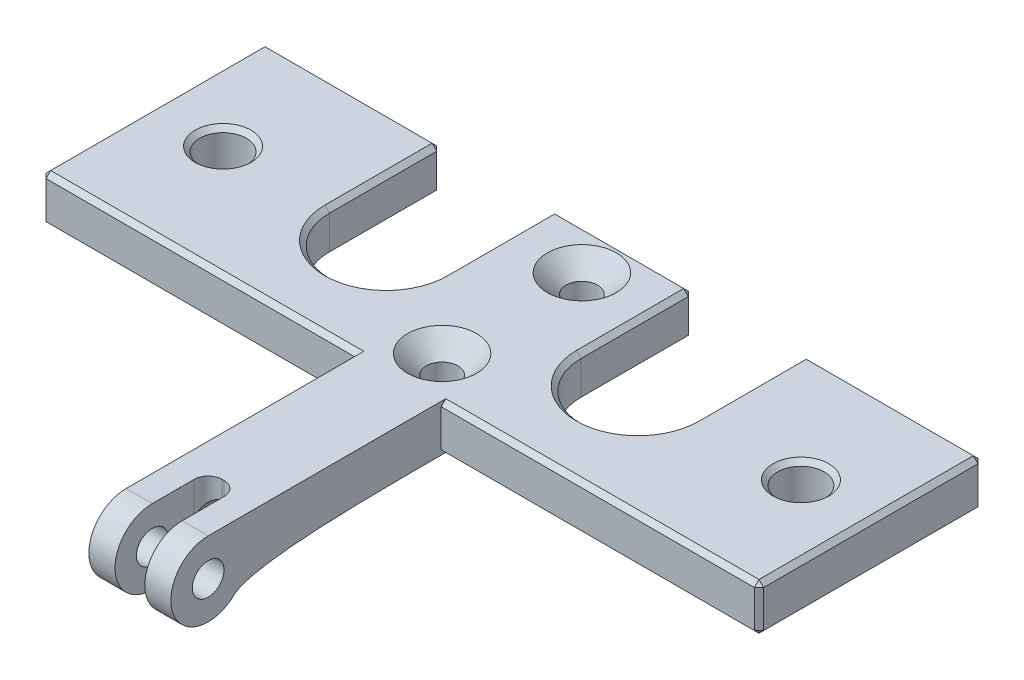
SolidWorks part; units mm, degrees
ref_plane "Front Plane" through (0, 0, 0) normal (0, 0, 1) x (1, 0, 0)
ref_plane "Top Plane" through (0, 0, 0) normal (0, 1, 0) x (1, 0, 0)
ref_plane "Right Plane" through (0, 0, 0) normal (1, 0, 0) x (0, 0, -1)
sketch "Sketch1" plane through (0, 0, 0) normal (0, 1, 0) x (1, 0, 0)
  line L0 (0, 0) -> (0, 50000) construction
  line L1 (38.5, -12) -> (-38.5, -12)
  line L2 (38.5, -12) -> (38.5, 12)
  line L3 (38.5, 12) -> (-38.5, 12)
  line L4 (-38.5, -12) -> (-38.5, 12)
  line L5 (38.5, -12) -> (-38.5, 12) construction
  line L6 (38.5, 12) -> (-38.5, -12) construction
  line L7 (0, 0) -> (50000, 0) construction
  line L8 (-19.575, 0) -> (-19.575, 12)
  line L9 (-7.425, 0) -> (-7.425, 12)
  line L10 (7.425, 0) -> (7.425, 12)
  line L11 (19.575, 0) -> (19.575, 12)
  circle A0 centre (-31, 0) radius 2.5
  circle A1 centre (-13.5, 0) radius 6.075
  circle A2 centre (31, 0) radius 2.5
  circle A3 centre (13.5, 0) radius 6.075
  circle A4 centre (0, -7.5) radius 1.7
  circle A5 centre (0, 7.5) radius 1.7
  point P0 (0, 0)
  dimension "D3" = 27
  dimension "D5" = 5
  dimension "D6" = 12.15
  dimension "D7" = 3.4
  dimension "D1" = 24
  dimension "D2" = 77
  dimension "D4" = 62
  dimension "D8" = 7.5
  dimension "D9" = 7.5
extrude "Boss-Extrude1" add sketch "Sketch1" along normal blind 5 contours L11 A3 L10 L3 L9 A1 L8 L4 L1 L2 A2 A0 region at (0, 0, 1.0489)
chamfer "Chamfer2" distance 2 angle 45 2 edges at (0, 5, -5.8) (0, 5, 9.2)
sketch "Sketch2" plane through (0, 0, 0) normal (0, -1, 0) x (1, 0, 0)
  line L9 (-5.025, 0) -> (-5.025, -12)
  line L10 (-21.975, -12) -> (-21.975, 0)
  line L11 (-5.025, 0) -> (-5.025, -12)
  line L12 (-21.975, -12) -> (-21.975, 0)
  line L14 (21.975, -12) -> (5.025, -12)
  line L15 (-5.025, -12) -> (-21.975, -12)
  line L16 (21.975, 0) -> (21.975, -12)
  line L17 (5.025, -12) -> (5.025, 0)
  line L18 (21.975, 0) -> (21.975, -12)
  line L19 (5.025, -12) -> (5.025, 0)
  arc A7 (-5.025, 0) -> (-21.975, 0) centre (-13.5, 0) ccw
  arc A8 (-5.025, 0) -> (-21.975, 0) centre (-13.5, 0) ccw
  arc A12 (21.975, 0) -> (5.025, 0) centre (13.5, 0) ccw
  arc A13 (21.975, 0) -> (5.025, 0) centre (13.5, 0) ccw
  dimension "D1" = 2.4
  dimension "D2" = 2.4
extrude "Cut-Extrude1" cut sketch "Sketch2" against normal blind 0.4
chamfer "Chamfer3" distance 0.5 angle 45 46 edges at (-31, 0, 2.5) (-31, 5, 2.5) (31, 0, 2.5) (31, 5, 2.5) (19.575, 5, -6) (7.425, 5, -6) (13.5, 5, 6.075) (38.5, 5, 0) (0, 5, 12) (38.5, 2.5, 12) (-38.5, 5, 0) (-38.5, 2.5, 12) (-19.575, 2.7, -12) (-29.0375, 5, -12) (-38.5, 2.5, -12) (-30.2375, 0, -12) (-38.5, 0, 0) (0, 0, 12) (38.5, 0, 0) (38.5, 2.5, -12) (29.0375, 5, -12) (19.575, 2.7, -12) (30.2375, 0, -12) (7.425, 2.7, -12) (0, 5, -12) (-7.425, 2.7, -12) (-19.575, 5, -6) (-7.425, 5, -6) (-13.5, 5, 6.075) (0, 0, 9.2) (0, 0, -5.8) (7.425, 0.4, -6) (19.575, 0.4, -6) (13.5, 0.4, 6.075) (-20.775, 0.4, -12) (-21.975, 0.2, -12) (20.775, 0.4, -12) (21.975, 0.2, -12) (5.025, 0.2, -12) (6.225, 0.4, -12) (-6.225, 0.4, -12) (-5.025, 0.2, -12) (0, 0, -12) (-7.425, 0.4, -6) (-19.575, 0.4, -6) (-13.5, 0.4, 6.075)
sketch "Sketch4" plane through (0, 0, 0) normal (1, 0, 0) x (0, 0, -1)
  line L0 (-12, 0.5) -> (-12, 4.5) construction
  line L1 (-11.5, 5) -> (11.5, 5) construction
  line L2 (-37, 5) -> (-11.5, 5)
  line L3 (-11.5, 5) -> (-11.5, 0)
  line L4 (11.5, 0) -> (-11.5, 0) construction
  line L5 (-36.9087, -4.4289) -> (-31.3424, 0.8557) construction
  arc A0 (-37, 5) -> (-34.2459, -1.9009) centre (-37, 1) ccw
  circle A1 centre (-37, 1) radius 1.7
  spline S0 degree 3 poles (-11.5, 0) (-17.5192, 0) (-32.1175, 0.1198) (-34.2459, -1.9009) knots 0 0 0 0 1 1 1 1
  dimension "D1" = 8
  dimension "D2" = 3.4
  dimension "D3" = 25
extrude "Boss-Extrude3" add sketch "Sketch4" along normal blind 2.8 from offset 1.6
extrude "Boss-Extrude4" add sketch "Sketch4<2>" against normal blind 2.8 from offset 1.6 offset against normal yes
sketch "Sketch4<2>" plane through (0, 0, 0) normal (1, 0, 0) x (0, 0, -1) same geometry as "Sketch4"
sketch "Sketch5" plane through (0, 5, 0) normal (0, 1, 0) x (1, 0, 0)
  line L0 (-1.6, -11.5) -> (-1.6, -37) construction
  line L1 (1.6, -11.5) -> (-1.6, -11.5)
  line L2 (1.6, -11.5) -> (1.6, -31)
  line L3 (1.6, -31) -> (-1.6, -31)
  line L4 (-1.6, -11.5) -> (-1.6, -31)
  line L5 (-4.4, -37) -> (-1.6, -37) construction
  dimension "D1" = 6
extrude "Boss-Extrude5" add sketch "Sketch5" against normal blind 2
fillet "Fillet1" radius 1.5 5 edges at (0, 3, 12) (1.6, 3, 21.5) (-1.6, 3, 21.5) (-1.6, 4, 31) (1.6, 4, 31)
